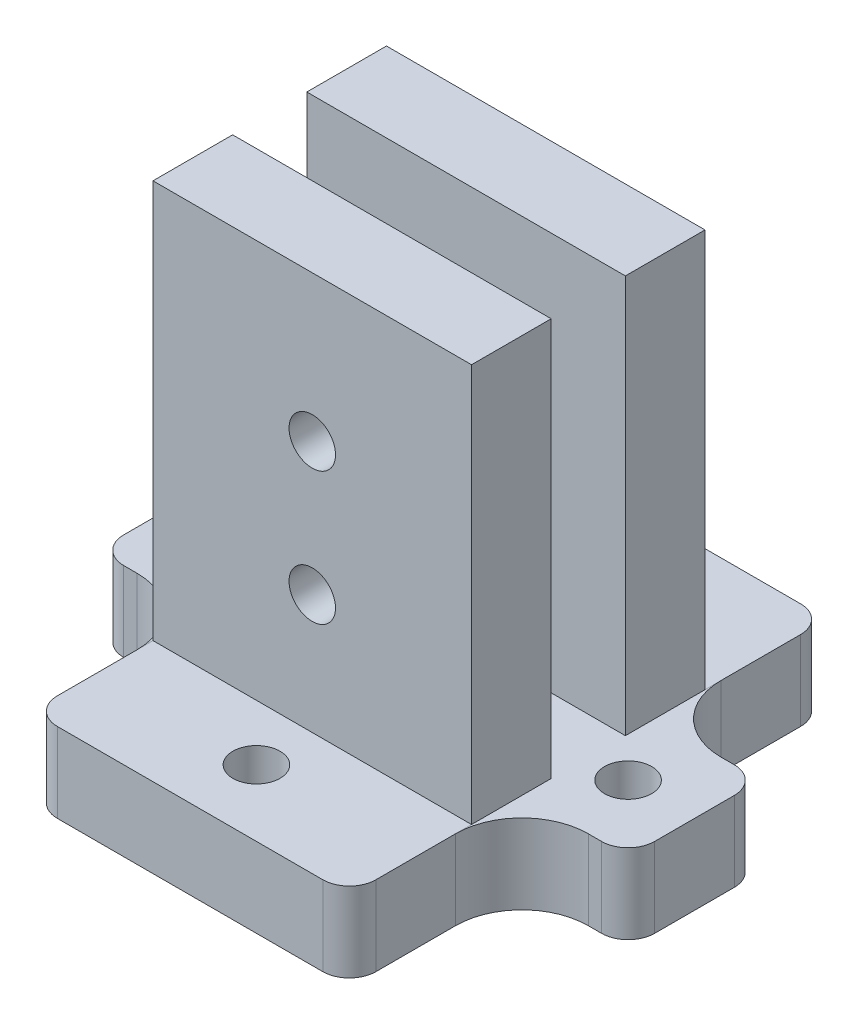
SolidWorks part; units mm, degrees
ref_plane "Front Plane" through (0, 0, 0) normal (0, 0, 1) x (1, 0, 0)
ref_plane "Top Plane" through (0, 0, 0) normal (0, 1, 0) x (1, 0, 0)
ref_plane "Right Plane" through (0, 0, 0) normal (1, 0, 0) x (0, 0, -1)
sketch "Sketch1" plane through (0, 0, 0) normal (0, 1, 0) x (1, 0, 0)
  line L1 (-10.1033, 11.3321) -> (13.8967, 11.3321)
  line L2 (-10.1033, 11.3321) -> (-10.1033, -12.6679)
  line L3 (-10.1033, -12.6679) -> (13.8967, -12.6679)
  line L4 (13.8967, 11.3321) -> (13.8967, -12.6679)
  dimension "D1" = 24
  dimension "D2" = 24
extrude "Boss-Extrude1" add sketch "Sketch1" along normal blind 6
sketch "Sketch2" plane through (0, 6, 0) normal (0, 1, 0) x (1, 0, 0)
  line L0 (-10.1033, 11.3321) -> (-10.1033, -12.6679) construction
  line L1 (-10.1033, -9.4629) -> (13.8967, -9.4629)
  line L2 (-10.1033, -9.4629) -> (-10.1033, -3.4629)
  line L3 (-10.1033, -3.4629) -> (13.8967, -3.4629)
  line L4 (13.8967, -9.4629) -> (13.8967, -3.4629)
  line L5 (13.8967, -12.6679) -> (13.8967, 11.3321) construction
  line L6 (-18.4237, -0.6679) -> (25.1046, -0.6679) construction
  line L7 (-10.1033, 2.1271) -> (13.8967, 2.1271)
  line L8 (-10.1033, 2.1271) -> (-10.1033, 8.1271)
  line L9 (-10.1033, 8.1271) -> (13.8967, 8.1271)
  line L10 (13.8967, 2.1271) -> (13.8967, 8.1271)
  dimension "D1" = 5.59
  dimension "D2" = 6
extrude "Boss-Extrude2" add sketch "Sketch2" along normal blind 30
sketch "Sketch3" plane through (0, 0, 12.6679) normal (0, 0, 1) x (1, 0, 0)
  line L4 (-10.1033, 0) -> (13.8967, 0)
  line L5 (13.8967, 0) -> (13.8967, 6)
  line L6 (13.8967, 6) -> (-10.1033, 6)
  line L7 (-10.1033, 6) -> (-10.1033, 0)
  line L8 (-10.1033, 0) -> (13.8967, 0)
  line L9 (13.8967, 0) -> (13.8967, 6)
  line L10 (13.8967, 6) -> (-10.1033, 6)
  line L11 (-10.1033, 6) -> (-10.1033, 0)
  dimension "D1" = 0
extrude "Boss-Extrude3" add sketch "Sketch3" along normal blind 6
sketch "Sketch4" plane through (0, 0, -11.3321) normal (0, 0, -1) x (-1, 0, 0)
  line L4 (-13.8967, 0) -> (10.1033, 0)
  line L5 (10.1033, 0) -> (10.1033, 6)
  line L6 (10.1033, 6) -> (-13.8967, 6)
  line L7 (-13.8967, 6) -> (-13.8967, 0)
  line L8 (-13.8967, 0) -> (10.1033, 0)
  line L9 (10.1033, 0) -> (10.1033, 6)
  line L10 (10.1033, 6) -> (-13.8967, 6)
  line L11 (-13.8967, 6) -> (-13.8967, 0)
  dimension "D1" = 0
extrude "Boss-Extrude4" add sketch "Sketch4" along normal blind 6
sketch "Sketch5" plane through (13.8967, 0, 0) normal (1, 0, 0) x (0, 0, -1)
  line L0 (-0.6679, 21.637) -> (-0.6679, 0) construction
  line L1 (-18.6679, 0) -> (17.3321, 0) construction
  line L2 (-3.4629, 6) -> (2.1271, 6) construction
  line L3 (-5.6679, 0) -> (4.3321, 0)
  line L4 (-5.6679, 0) -> (-5.6679, 6)
  line L5 (-5.6679, 6) -> (4.3321, 6)
  line L6 (4.3321, 0) -> (4.3321, 6)
  dimension "D1" = 10
extrude "Boss-Extrude5" add sketch "Sketch5" along normal blind 8
fillet "Fillet1" radius 5 2 edges
fillet "Fillet2" radius 2 2 edges at (21.8967, 3, -4.3321) (21.8967, 3, 5.6679)
fillet "Fillet3" radius 2 4 edges at (-10.1033, 3, -17.3321) (13.8967, 3, -17.3321) (-10.1033, 3, 18.6679) (13.8967, 3, 18.6679)
sketch "Sketch6" plane through (-10.1033, 0, 0) normal (-1, 0, 0) x (0, 0, 1)
  line L0 (0.6679, 0) -> (0.6679, 18.2836) construction
  line L1 (-15.3321, 0) -> (16.6679, 0) construction
  line L2 (-2.1271, 6) -> (3.4629, 6) construction
  line L3 (-4.3321, 0) -> (5.6679, 0)
  line L4 (-4.3321, 0) -> (-4.3321, 6)
  line L5 (-4.3321, 6) -> (5.6679, 6)
  line L6 (5.6679, 0) -> (5.6679, 6)
  dimension "D1" = 10
extrude "Boss-Extrude6" add sketch "Sketch6" along normal blind 8
fillet "Fillet4" radius 5 2 edges at (-10.1033, 3, 5.6679) (-10.1033, 3, -4.3321)
fillet "Fillet5" radius 2 2 edges at (-18.1033, 3, 5.6679) (-18.1033, 3, -4.3321)
sketch "Sketch7" plane through (0, 6, 0) normal (0, 1, 0) x (1, 0, 0)
  line L2 (-18.1033, -0.6679) -> (21.8967, -0.6679) construction
  line L3 (1.8967, -18.6679) -> (1.8967, 17.3321) construction
  line L4 (11.8967, -18.6679) -> (-8.1033, -18.6679) construction
  line L5 (-8.1033, 17.3321) -> (11.8967, 17.3321) construction
  line L6 (-18.1033, -3.6679) -> (-18.1033, 2.3321) construction
  line L7 (21.8967, 2.3321) -> (21.8967, -3.6679) construction
  circle A0 centre (1.8967, -13.6679) radius 1.775
  circle A2 centre (-13.1033, -0.6679) radius 1.775
  circle A3 centre (1.8967, 12.3321) radius 1.775
  circle A4 centre (16.8967, -0.6679) radius 1.775
  dimension "D5" = 3.55
  dimension "D1" = 5
  dimension "D2" = 5
  dimension "D3" = 5
  dimension "D4" = 5
extrude "Cut-Extrude1" cut sketch "Sketch7" against normal through all
sketch "Sketch8" plane through (0, 0, 9.4629) normal (0, 0, 1) x (1, 0, 0)
  line L0 (1.8967, 15) -> (1.8967, 25) construction
  line L1 (1.8967, 25) -> (1.8967, 36) construction
  line L2 (-10.1033, 36) -> (13.8967, 36) construction
  line L3 (-8.1033, 0) -> (11.8967, 0) construction
  circle A0 centre (1.8967, 15) radius 1.75
  circle A1 centre (1.8967, 25) radius 1.75
  dimension "D3" = 3.5
  dimension "D1" = 15
  dimension "D2" = 25
extrude "Cut-Extrude2" cut sketch "Sketch8" against normal up to surface (17.59 mm away) up to face at (1.8967, 21, -8.1271)
